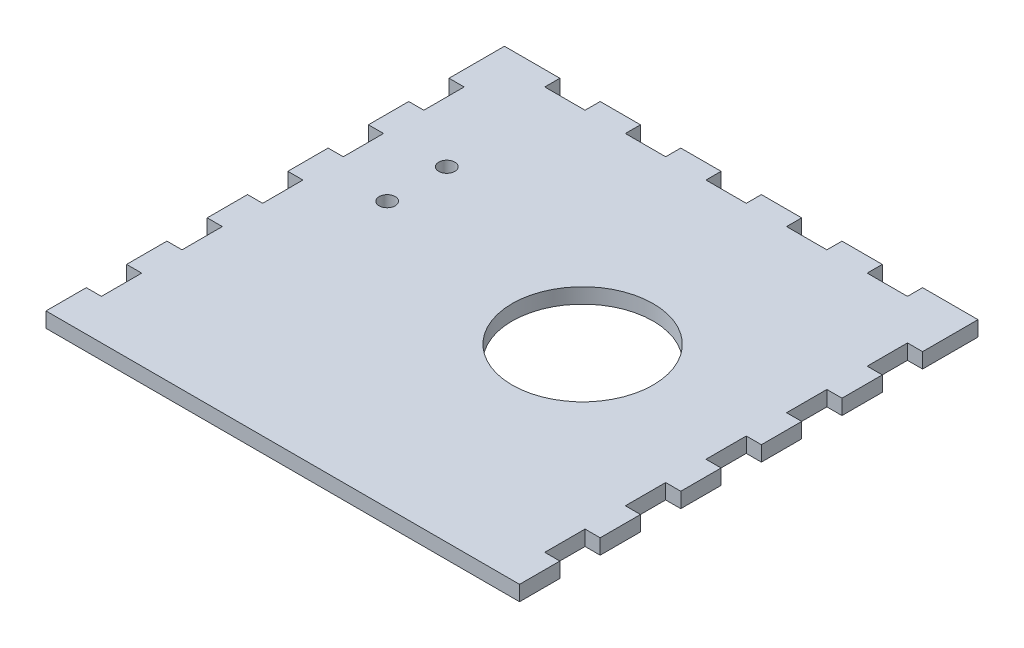
SolidWorks part; units mm, degrees
ref_plane "Front Plane" through (0, 0, 0) normal (0, 0, 1) x (1, 0, 0)
ref_plane "Top Plane" through (0, 0, 0) normal (0, 1, 0) x (1, 0, 0)
ref_plane "Right Plane" through (0, 0, 0) normal (1, 0, 0) x (0, 0, -1)
sketch "Sketch1" plane through (0, 0, 0) normal (0, 1, 0) x (1, 0, 0)
  line L1 (-139.7, -139.7) -> (139.7, -139.7)
  line L2 (-139.7, -139.7) -> (-139.7, 139.7)
  line L3 (-139.7, 139.7) -> (139.7, 139.7)
  line L4 (139.7, -139.7) -> (139.7, 139.7)
  line L5 (-139.7, -139.7) -> (139.7, 139.7) construction
  line L6 (-139.7, 139.7) -> (139.7, -139.7) construction
  point P0 (0, 0)
  dimension "D1" = 279.4
  dimension "D2" = 279.4
extrude "Boss-Extrude1" add sketch "Sketch1" along normal blind 9.525
sketch "Sketch2" plane through (139.7, 0, 0) normal (1, 0, 0) x (0, 0, -1)
  line L0 (-139.7, 9.525) -> (139.7, 9.525) construction
  line L1 (-139.7, 0) -> (-114.3, 0)
  line L2 (-139.7, 0) -> (-139.7, 9.525)
  line L3 (-139.7, 9.525) -> (-114.3, 9.525)
  line L4 (-114.3, 0) -> (-114.3, 9.525)
  dimension "D1" = 25.4
extrude "Boss-Extrude2" add sketch "Sketch2" along normal blind 9.525
pattern_linear "LPattern1" count 6 spacing 50.8 along (0, 0, -1) of "Boss-Extrude2"
mirror "Mirror1" about plane through (0, 0, 0) normal (1, 0, 0) of "LPattern1"
sketch "Sketch3" plane through (0, 0, -139.7) normal (0, 0, -1) x (-1, 0, 0)
  line L0 (-149.225, 9.525) -> (149.225, 9.525) construction
  line L1 (-139.7, 9.525) -> (-114.3, 9.525)
  line L2 (-139.7, 9.525) -> (-139.7, 0)
  line L3 (-139.7, 0) -> (-114.3, 0)
  line L4 (-114.3, 9.525) -> (-114.3, 0)
  line L5 (-149.225, 0) -> (149.225, 0) construction
  line L6 (-149.225, 0) -> (-149.225, 9.525) construction
  dimension "D1" = 9.525
  dimension "D2" = 25.4
extrude "Boss-Extrude3" add sketch "Sketch3" along normal blind 9.525
pattern_linear "LPattern2" count 6 spacing 50.8 along (-1, 0, 0) of "Boss-Extrude3"
sketch "Sketch5" plane through (0, 0, -139.7) normal (0, 0, -1) x (-1, 0, 0)
  line L0 (158.9088, 0) -> (-158.9088, 0) construction
  line L1 (-149.225, 9.525) -> (-139.7, 9.525)
  line L2 (-149.225, 9.525) -> (-149.225, 0)
  line L3 (-149.225, 0) -> (-139.7, 0)
  line L4 (-139.7, 9.525) -> (-139.7, 0)
  line L5 (-139.7, 9.525) -> (-139.7, 0) construction
extrude "Boss-Extrude4" add sketch "Sketch5" along normal blind 9.525
mirror "Mirror2" about plane through (0, 0, 0) normal (1, 0, 0) of "Boss-Extrude4"
sketch "Sketch6" plane through (0, 9.525, 0) normal (0, 1, 0) x (1, 0, 0)
  line L0 (63.5, 139.7) -> (38.1, 139.7) construction
  line L1 (139.7, -12.7) -> (139.7, 12.7) construction
  circle A0 centre (38.1, 11.176) radius 44.45
  point P4 (0, 0)
  dimension "D1" = 128.524
  dimension "D2" = 101.6
extrude "Cut-Extrude1" cut sketch "Sketch6" against normal through all
sketch "Sketch7" plane through (0, 9.525, 0) normal (0, 1, 0) x (1, 0, 0)
  line L0 (-139.7, 63.5) -> (-139.7, 38.1) construction
  line L1 (-139.7, 114.3) -> (-139.7, 88.9) construction
  line L2 (-88.9, 139.7) -> (-114.3, 139.7) construction
  circle A0 centre (-101.6, 65.278) radius 5.08
  circle A1 centre (-101.6, 27.686) radius 5.08
  point P4 (-98.8934, 29.22)
  dimension "D1" = 10.16
  dimension "D2" = 10.16
  dimension "D3" = 38.1
  dimension "D4" = 38.1
  dimension "D5" = 37.592
  dimension "D6" = 74.422
extrude "Cut-Extrude2" cut sketch "Sketch7" against normal through all
